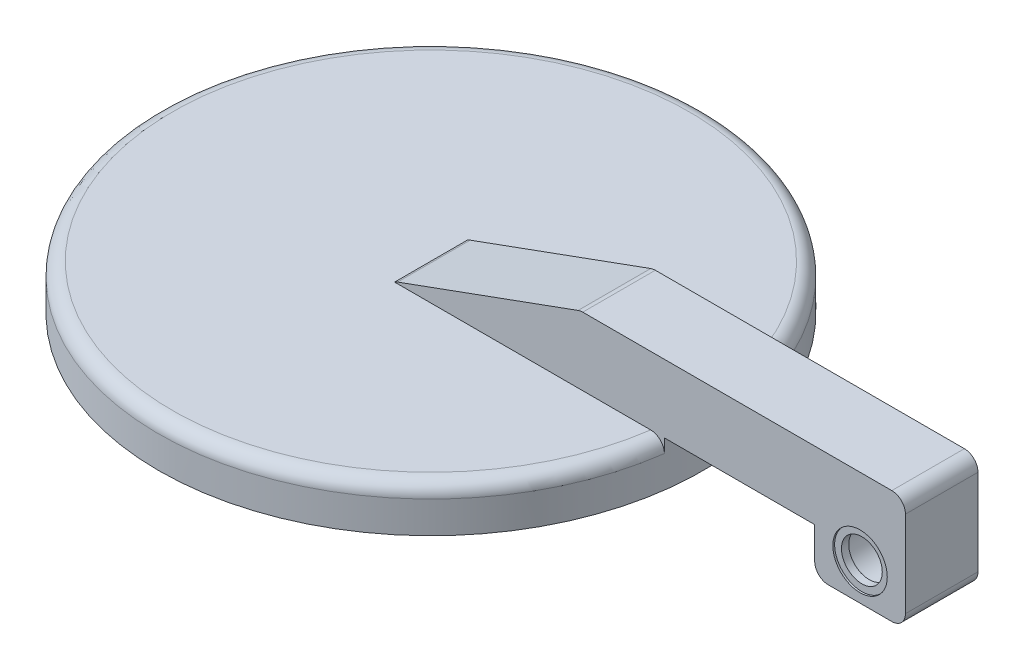
SolidWorks part; units mm, degrees
ref_plane "Front Plane" through (0, 0, 0) normal (0, 0, 1) x (1, 0, 0)
ref_plane "Top Plane" through (0, 0, 0) normal (0, 1, 0) x (1, 0, 0)
ref_plane "Right Plane" through (0, 0, 0) normal (1, 0, 0) x (0, 0, -1)
sketch "Sketch2" plane through (0, 0, 0) normal (0, 0, 1) x (1, 0, 0)
  line L7 (0, 0) -> (30, 0)
  line L8 (0, 0) -> (0, 5)
  line L9 (0, 5) -> (30, 5)
  line L10 (30, 0) -> (30, 5)
  dimension "D1" = 5
  dimension "D2" = 30
revolve "Revolve1" add sketch "Sketch2" angle 360 about L8
sketch "Sketch3" plane through (0, 5, 0) normal (0, 1, 0) x (1, 0, 0)
  line L0 (0, -10) -> (0, 10) construction
  line L1 (0, 10) -> (35, 10)
  line L2 (35, 10) -> (35, 6)
  line L3 (35, 6) -> (0, 6)
  line L4 (0, 10) -> (0, 6)
  line L5 (0, -10) -> (35, -10)
  line L6 (35, -10) -> (35, -6)
  line L7 (35, -6) -> (0, -6)
  line L8 (0, -6) -> (0, -10)
  line L9 (0, 4) -> (0, -4)
  line L10 (0, 4) -> (56.3, 4)
  line L11 (0, -4) -> (56.3, -4)
  line L12 (56.3, -4) -> (56.3, 4)
  point P4 (0, 0)
  point P13 (0, 0)
  circle M1 centre (0, 0) radius 30
  dimension "D1" = 20
  dimension "D2" = 35
  dimension "D3" = 4
  dimension "D4" = 8
  dimension "D5" = 56.3
extrude "Boss-Extrude1" add sketch "Sketch3" along normal blind 7.5 contours L9 L11 L10 M1 | L11 L12 L10 M1 region at (14.9555, 5, 0) region at (43.1053, 5, 0)
sketch "Sketch4" plane through (0, 0, 0) normal (0, 0, 1) x (1, 0, 0)
  line L5 (35, 8.75) -> (37.8, 8.75) construction
  line L7 (56.3, 8.75) -> (37.8, 8.75) construction
  line L8 (56.3, 12.5) -> (56.3, 5) construction
  line L10 (-0.1339, 5) -> (20.4721, 12.5)
  line L11 (29.7321, 5) -> (-30, 5) construction
  line L12 (0, 12.5) -> (56.3, 12.5) construction
  line L13 (0, 5) -> (29.7321, 5) construction
  line L14 (20.4721, 12.5) -> (0, 12.5)
  line L15 (0, 12.5) -> (-0.1339, 5)
  circle A0 centre (37.8, 8.75) radius 2
  dimension "D3" = 4
  dimension "D1" = 20
  dimension "D2" = 18.5
extrude "Cut-Extrude1" cut sketch "Sketch4" against normal mid plane 30 contours L14 L15 L10
sketch "Sketch6" plane through (0, 5, 0) normal (0, -1, 0) x (1, 0, 0)
  line L6 (56.3, 4) -> (46.3, 4)
  line L7 (56.3, 4) -> (56.3, -4) construction
  line L8 (29.7321, 4) -> (56.3, 4) construction
  line L9 (46.3, 4) -> (46.3, -4)
  line L10 (29.7321, -4) -> (56.3, -4) construction
  line L11 (46.3, -4) -> (56.3, -4)
  line L12 (56.3, -4) -> (56.3, 4)
  dimension "D1" = 10
extrude "Boss-Extrude2" add sketch "Sketch6" along normal blind 5
sketch "Sketch7" plane through (0, 0, 4) normal (0, 0, 1) x (1, 0, 0)
  line L0 (51.3, 4) -> (51.3, 0) construction
  line L2 (56.3, 0) -> (46.3, 0) construction
  circle A0 centre (51.3, 4) radius 3
  dimension "D2" = 6
  dimension "D1" = 4
extrude "Cut-Extrude2" cut sketch "Sketch7" against normal blind 10
fillet "Fillet2" radius 1.5 6 edges at (46.3, 0, 0) (56.3, 0, 0) (56.3, 12.5, 0) (20.4721, 12.5, 0) (0, 5.0487, 0) (-30, 5, 0)
sketch "Sketch9" plane through (0, 0, -4) normal (0, 0, -1) x (-1, 0, 0)
  circle A0 centre (-51.3, 4) radius 3
  circle A1 centre (-51.3, 4) radius 4
  dimension "D1" = 6
  dimension "D2" = 8
sketch "Sketch10" plane through (0, 0, 4) normal (0, 0, 1) x (1, 0, 0)
  circle A0 centre (51.3, 4) radius 3
  circle A1 centre (51.3, 4) radius 2.25
  dimension "D1" = 6
  dimension "D2" = 4.5
extrude "Boss-Extrude4" add sketch "Sketch10" along normal blind 0.8 from offset 1 offset against normal yes
